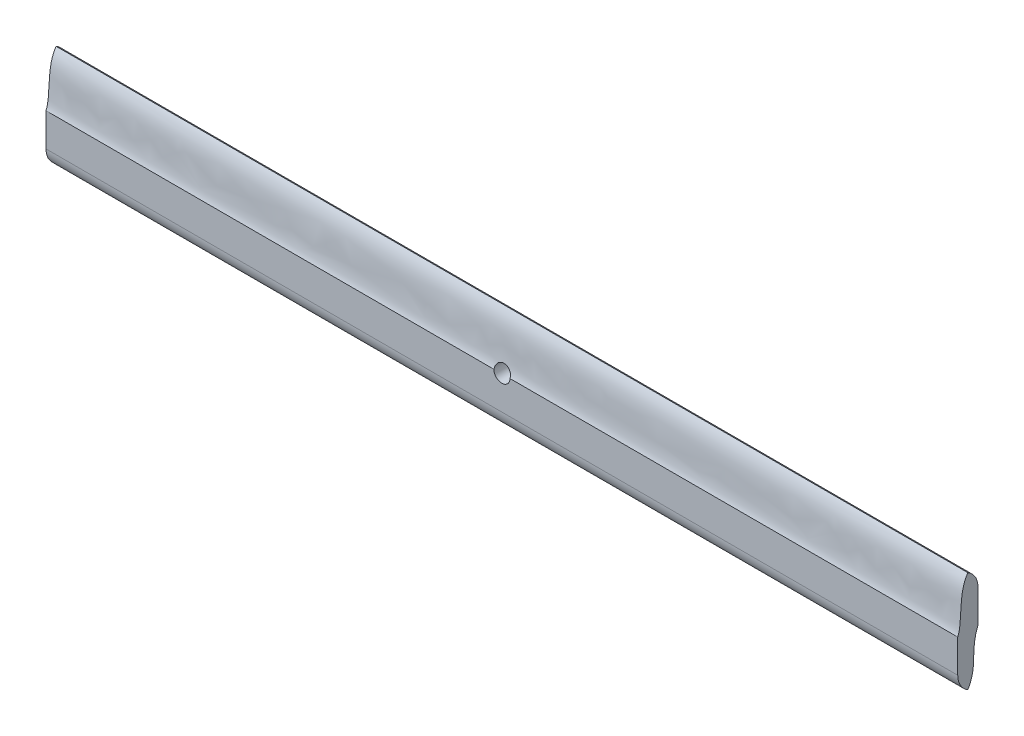
SolidWorks part; units mm, degrees
ref_plane "Front Plane" through (0, 0, 0) normal (0, 0, 1) x (1, 0, 0)
ref_plane "Top Plane" through (0, 0, 0) normal (0, 1, 0) x (1, 0, 0)
ref_plane "Right Plane" through (0, 0, 0) normal (1, 0, 0) x (0, 0, -1)
sketch "Sketch2" plane through (0, 0, 0) normal (0, 0, 1) x (1, 0, 0)
  circle A0 centre (0, 0) radius 0.4
  circle A1 centre (0, 0) radius 1.2
  dimension "D1" = 0.8
  dimension "D2" = 0.8
extrude "Boss-Extrude1" add sketch "Sketch2" along normal blind 1
sketch "Sketch3" plane through (0, 0, 1) normal (0, 0, 1) x (1, 0, 0)
  line L0 (0, 2.5) -> (22.5, 2.5)
  line L1 (0, 2.5) -> (0, -2.5)
  line L2 (22.5, 2.5) -> (22.5, -2.5)
  line L3 (0, -2.5) -> (22.5, -2.5)
  line L4 (0, 2.5) -> (-22.5, 2.5)
  line L5 (0, 2.5) -> (0, -2.5)
  line L6 (-22.5, 2.5) -> (-22.5, -2.5)
  line L7 (0, -2.5) -> (-22.5, -2.5)
  circle A0 centre (0, 0) radius 1.2
  point P0 (0, 0)
  circle M9 centre (0, 0) radius 1.2
  dimension "D1" = 45
  dimension "D2" = 5
extrude "Boss-Extrude4" add sketch "Sketch3" against normal blind 1 contours L1 L3 L2 L0 M9 | L7 L1 L4 L6 M9 region at (11.4704, 0, 1) region at (-11.4704, 0, 1)
sketch "Sketch4" plane through (22.5, 0, 0) normal (1, 0, 0) x (0, 0, -1)
  line L0 (-1, 2.5) -> (-1, -2.5) construction
  line L1 (0, 2.5) -> (-1, 2.5) construction
  line L2 (-0.5, 2.5) -> (-1, 1.7961) construction
  line L3 (-1, 1.7961) -> (-0.7327, 0.6192) construction
  line L4 (-0.7327, 0.6192) -> (-1, 0) construction
  line L5 (-1, 0) -> (-1, 2.5)
  line L6 (0, 2.5) -> (0, -2.5) construction
  line L7 (-1, 2.5) -> (-0.5, 2.5)
  line L10 (0, -2.5) -> (-1, -2.5) construction
  line L12 (-0.5, -2.5) -> (0, -1.6692) construction
  line L13 (0, -1.6692) -> (-0.3991, -0.926) construction
  line L14 (-0.3991, -0.926) -> (0, 0) construction
  line L15 (0, 0) -> (0, -2.5)
  line L17 (0, -2.5) -> (-0.5, -2.5)
  spline S0 degree 3 poles (-0.5, 2.5) (-1, 1.7961) (-0.7327, 0.6192) (-1, 0) knots 0 0 0 0 1 1 1 1
  spline S1 degree 3 poles (-0.5, -2.5) (0, -1.6692) (-0.3991, -0.926) (0, 0) knots 0 0 0 0 1 1 1 1
  spline S2 degree 1 poles (-0.5, 2.5) (0, 2.5) knots 0 0 1 1
  point P20 (0, 0)
  line M12 (-1, -2.5) -> (0, -2.5)
  line M13 (0, -2.5) -> (0, 2.5)
extrude "Cut-Extrude1" cut sketch "Sketch4" against normal up to next contours S1 M12 M13 | S0 L5 L7 region at (22.5, -1.5646, 0.1346)
fillet "Fillet2" radius 1 2 edges at (0, -2.5, 1) (0, 2.5, 0)
